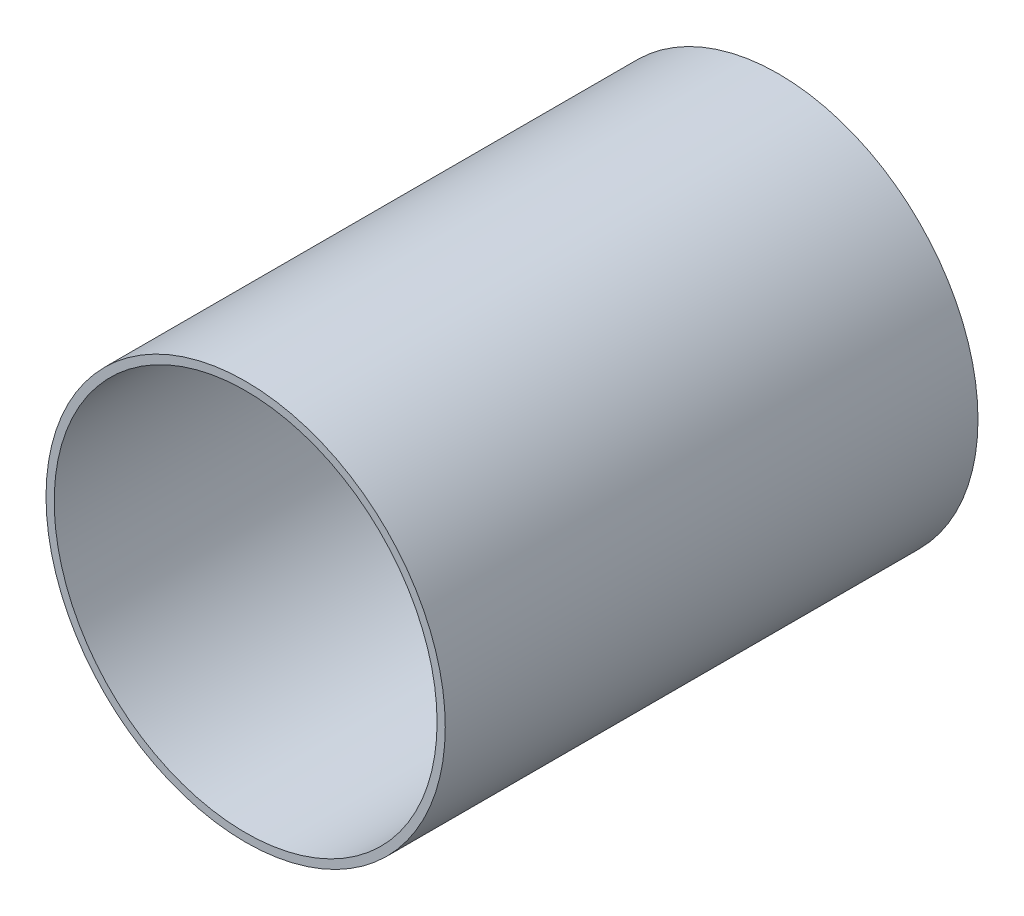
SolidWorks part; units mm, degrees
ref_plane "Front Plane" through (0, 0, 0) normal (0, 0, 1) x (1, 0, 0)
ref_plane "Top Plane" through (0, 0, 0) normal (0, 1, 0) x (1, 0, 0)
ref_plane "Right Plane" through (0, 0, 0) normal (1, 0, 0) x (0, 0, -1)
sketch "Sketch1" plane through (0, 0, 0) normal (0, 0, 1) x (1, 0, 0)
  circle A0 centre (0, 0) radius 38.0746
  circle A1 centre (0, 0) radius 36.5125
  dimension "D1" = 73.025
  dimension "D2" = 76.1492
extrude "Boss-Extrude1" add sketch "Sketch1" along normal mid plane 101.6
equation "\"AIRFRAME_OD\"= 3.091in"
equation "\"AIRFRAME_ID\"= 3.00in"
equation "\"FLAT_T\" = 0.125in"
equation "\"NOSE_EXP_L\"= 3.5in"
equation "\"NOSE_SHOULDER_L\" = 5in"
equation "\"MAIN_L\" = 30in"
equation "\"RECO_COUP_L\" = 6in"
equation "\"RECO_SWITCH_L\" = 1.5in"
equation "\"DROGUE_L\" = 14in"
equation "\"ATS_FORE_COUP_L\" = 4in"
equation "\"ATS_AFT_COUP_L\" = 2.5in"
equation "\"LOWER_L\" = 16in"
equation "\"FIN_N\" = 4"
equation "\"CR_AFT_X\" = 0.5in"
equation "\"CR_FORE_X\" = 6in"
equation "\"D1@Sketch1\"=\"COUPLER_ID\""
equation "\"D2@Sketch1\"=\"COUPLER_OD\""
equation "\"D1@Boss-Extrude1\"=\"ATS_FORE_COUP_L\""
equation "\"FIN_ROOT\" = 5in"
equation "\"FIN_X\" = 0.75in"
equation "\"MOTOR_OD\" = 2.25in"
equation "\"MOTOR_ID\" = 2.126in"
equation "\"COUPLER_OD\" = 2.998in"
equation "\"COUPLER_ID\" = 2.875in"
